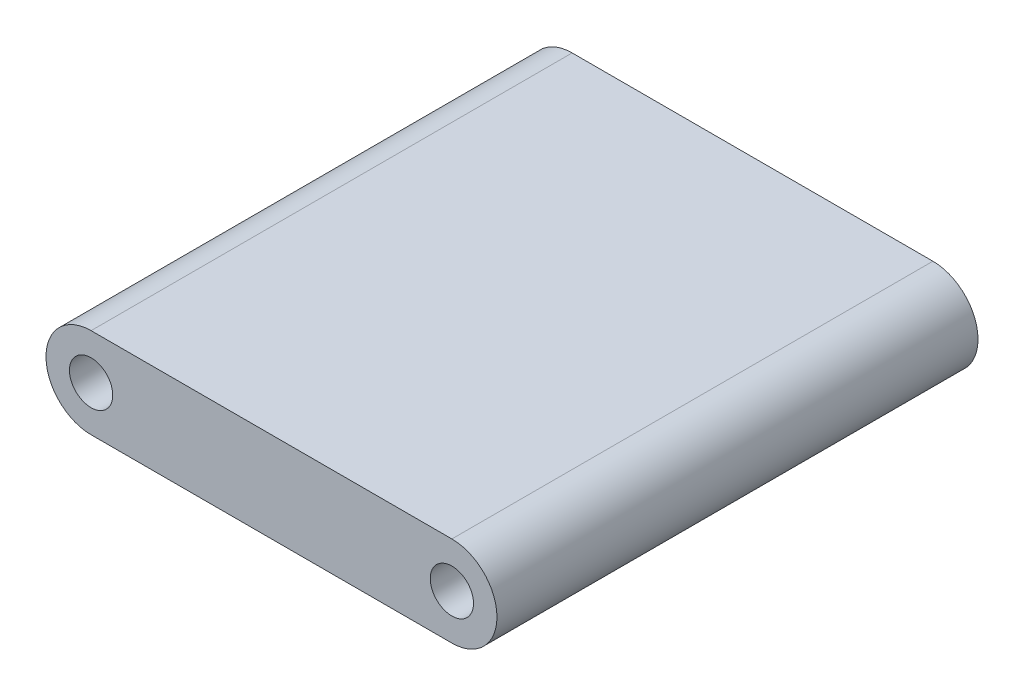
SolidWorks part; units mm, degrees
ref_plane "Front Plane" through (0, 0, 0) normal (0, 0, 1) x (1, 0, 0)
ref_plane "Top Plane" through (0, 0, 0) normal (0, 1, 0) x (1, 0, 0)
ref_plane "Right Plane" through (0, 0, 0) normal (1, 0, 0) x (0, 0, -1)
sketch "Sketch1" plane through (0, 0, 0) normal (0, 0, 1) x (1, 0, 0)
  line L0 (0, 0) -> (38.1, 0) construction
  line L1 (0, 4.7625) -> (38.1, 4.7625)
  line L2 (0, -4.7625) -> (38.1, -4.7625)
  arc A0 (0, 4.7625) -> (0, -4.7625) centre (0, 0) ccw
  arc A1 (38.1, -4.7625) -> (38.1, 4.7625) centre (38.1, 0) ccw
  circle A2 centre (0, 0) radius 2.286
  circle A3 centre (38.1, 0) radius 2.286
  point P3 (19.05, 0)
  dimension "D3" = 4.572
  dimension "D4" = 4.572
  dimension "D1" = 9.525
  dimension "D2" = 38.1
extrude "Boss-Extrude1" add sketch "Sketch1" along normal blind 50.8
